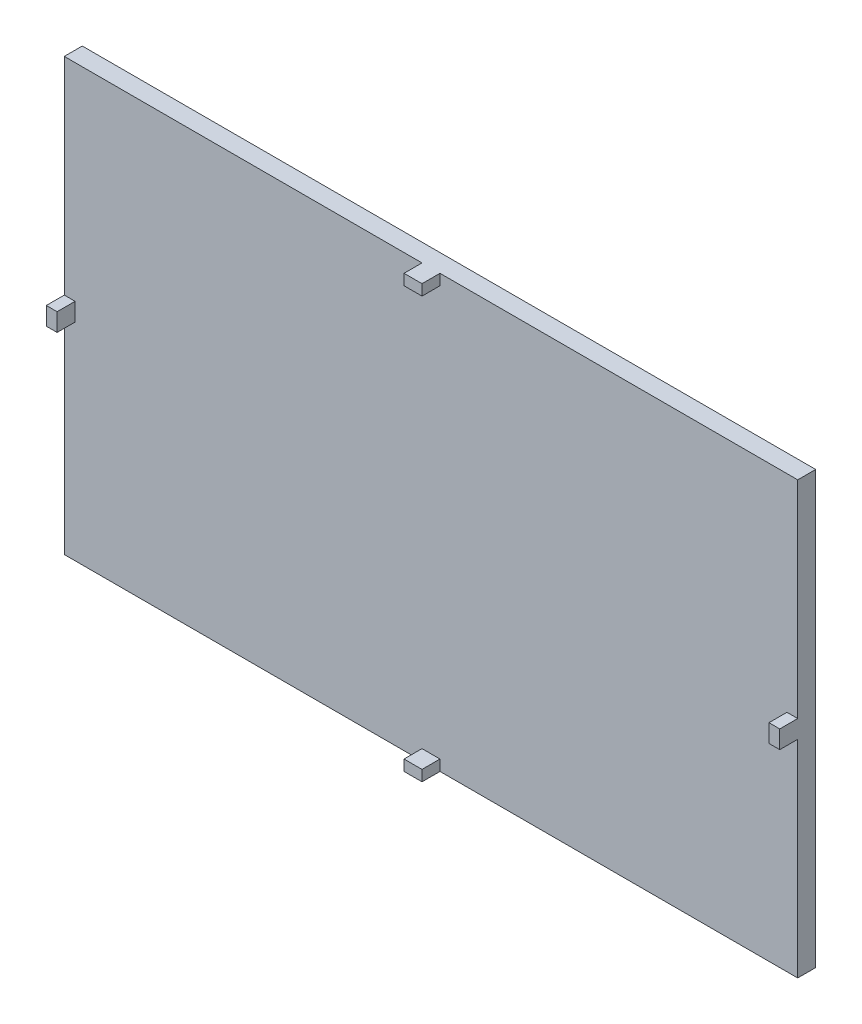
SolidWorks part; units mm, degrees
ref_plane "Plano frontal" through (0, 0, 0) normal (0, 0, 1) x (1, 0, 0)
ref_plane "Plano superior" through (0, 0, 0) normal (0, 1, 0) x (1, 0, 0)
ref_plane "Plano direito" through (0, 0, 0) normal (1, 0, 0) x (0, 0, -1)
sketch "Esboço1" plane through (0, 0, 0) normal (0, 0, 1) x (1, 0, 0)
  line L1 (-51.4207, 30.869) -> (152.5793, 30.869)
  line L2 (-51.4207, 30.869) -> (-51.4207, -89.131)
  line L3 (-51.4207, -89.131) -> (152.5793, -89.131)
  line L4 (152.5793, 30.869) -> (152.5793, -89.131)
  dimension "D1" = 204
  dimension "D2" = 120
extrude "Ressalto-extrusão1" add sketch "Esboço1" along normal blind 5 contours L1 L4 L3 L2
sketch "Esboço2" plane through (0, 0, 5) normal (0, 0, 1) x (1, 0, 0)
  line L1 (-51.4207, 30.869) -> (152.5793, 30.869) construction
  line L2 (53.0793, 30.869) -> (48.0793, 30.869)
  line L3 (53.0793, 30.869) -> (53.0793, 27.869)
  line L4 (53.0793, 27.869) -> (48.0793, 27.869)
  line L5 (48.0793, 30.869) -> (48.0793, 27.869)
  line L6 (-51.4207, -89.131) -> (152.5793, -89.131) construction
  line L7 (53.0793, -89.131) -> (48.0793, -89.131)
  line L8 (53.0793, -89.131) -> (53.0793, -86.131)
  line L10 (53.0793, -86.131) -> (48.0793, -86.131)
  line L11 (48.0793, -89.131) -> (48.0793, -86.131)
  line L12 (-51.4207, 30.869) -> (-51.4207, -89.131) construction
  line L13 (-51.4207, -26.631) -> (-48.4207, -26.631)
  line L15 (-51.4207, -26.631) -> (-51.4207, -31.631)
  line L16 (-51.4207, -31.631) -> (-48.4207, -31.631)
  line L17 (-48.4207, -26.631) -> (-48.4207, -31.631)
  line L18 (152.5793, 30.869) -> (152.5793, -89.131) construction
  line L19 (152.5793, -26.631) -> (149.5793, -26.631)
  line L20 (152.5793, -26.631) -> (152.5793, -31.631)
  line L21 (152.5793, -31.631) -> (149.5793, -31.631)
  line L22 (149.5793, -26.631) -> (149.5793, -31.631)
  dimension "D2" = 3
  dimension "D3" = 3
  dimension "D1" = 3
  dimension "D4" = 3
  dimension "D5" = 5
  dimension "D6" = 5
  dimension "D7" = 5
  dimension "D8" = 5
  dimension "D9" = 57.5
  dimension "D10" = 57.5
  dimension "D11" = 99.5
  dimension "D12" = 99.5
extrude "Ressalto-extrusão2" add sketch "Esboço2" along normal blind 5 contours L2 L5 L4 L3 | L15 L16 L17 L13 | L7 L11 L10 L8 | L20 L21 L22 L19
